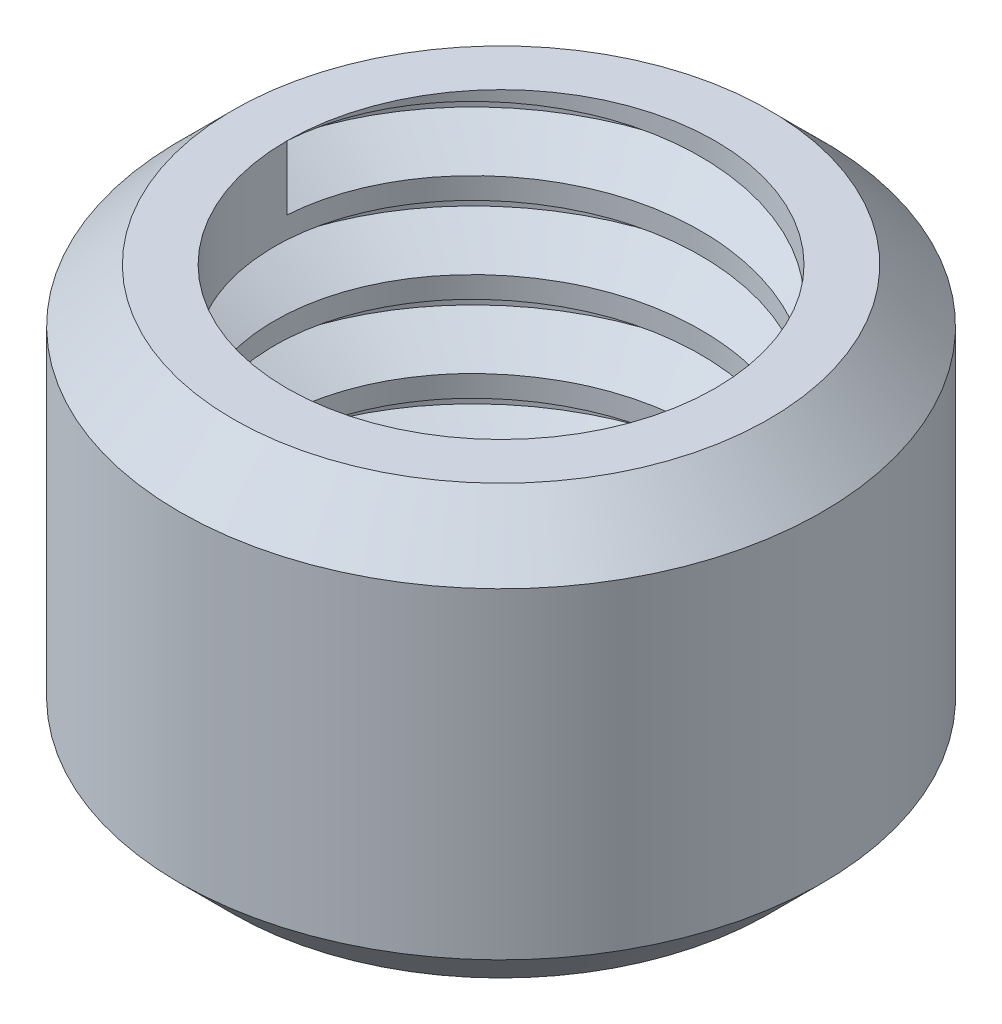
SolidWorks part; units mm, degrees
ref_plane "Front Plane" through (0, 0, 0) normal (0, 0, 1) x (1, 0, 0)
ref_plane "Top Plane" through (0, 0, 0) normal (0, 1, 0) x (1, 0, 0)
ref_plane "Right Plane" through (0, 0, 0) normal (1, 0, 0) x (0, 0, -1)
sketch "Sketch1" plane through (0, 0, 0) normal (0, 1, 0) x (1, 0, 0)
  circle A0 centre (0, 0) radius 1.5
extrude "Boss-Extrude1" add sketch "Sketch1" along normal blind 2
sketch "Sketch2" plane through (0, 2, 0) normal (0, 1, 0) x (1, 0, 0)
  circle A0 centre (0, 0) radius 1
extrude "Cut-Extrude1" cut sketch "Sketch2" against normal blind 3
thread "Thread1" pitch 0.4 method cut profile "Thread Profile1" start angle 0, offset 0, length 10, pitch 0.4, diameter 2
ref_plane "Plane1" through (-1, 2, 0) normal (0, 0, 1) x (-1, 0, 0)
sketch "Thread Profile1" plane through (-1, 2, 0) normal (0, 0, 1) x (-1, 0, 0)
  line L0 (0, 0) -> (0, 0.4) construction
  line L1 (0, 0) -> (0.2165, 0.125)
  line L2 (0.2165, 0.125) -> (0.2165, 0.175)
  line L3 (0.2165, 0.175) -> (0, 0.3)
  line L4 (0.2165, 0.15) -> (0, 0.15) construction
  line L11 (0, 0) -> (0, 0.3)
  point P2 (0, 0)
  dimension "Pitch" = 0.4
  dimension "Profile_Angle" = 60
  dimension "Profile_Land" = 0.05
  dimension "Profile_Height" = 0.2165
chamfer "Chamfer1" distance 0.25 angle 45 2 edges at (0, 0, 1.5) (0, 2, 1.5)
